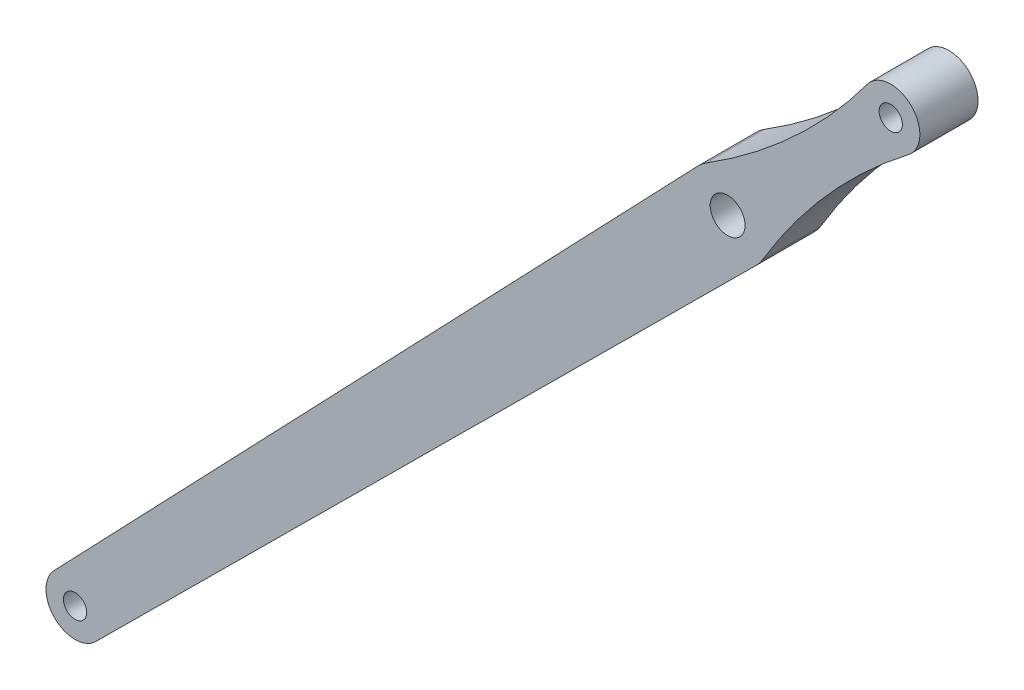
SolidWorks part; units mm, degrees
ref_plane "Front Plane" through (0, 0, 0) normal (0, 0, 1) x (1, 0, 0)
ref_plane "Top Plane" through (0, 0, 0) normal (0, 1, 0) x (1, 0, 0)
ref_plane "Right Plane" through (0, 0, 0) normal (1, 0, 0) x (0, 0, -1)
sketch "Sketch1" plane through (0, 0, 0) normal (0, 0, 1) x (1, 0, 0)
  line L0 (-124.7039, 115.7855) -> (-238.2136, 3.04) construction
  line L3 (-134.6926, 125.5935) -> (-245.3484, 10.0457) construction
  line L4 (-124.7039, 115.7855) -> (-238.2136, 3.04)
  line L5 (-134.6926, 125.5935) -> (-245.3484, 10.0457)
  arc A5 (-98.5698, 145.3249) -> (-123.6242, 117.1676) centre (-37.7285, 65.9629) ccw construction
  arc A6 (-133.3304, 126.6982) -> (-105.6348, 152.2622) centre (-186.0937, 211.6455) ccw construction
  circle A13 centre (-101.6119, 149.293) radius 5 construction
  circle A14 centre (-241.7372, 6.5874) radius 5 construction
  circle A15 centre (-129.6369, 120.7519) radius 7 construction
  circle A16 centre (-101.6119, 149.293) radius 2 construction
  circle A17 centre (-129.6369, 120.7519) radius 3 construction
  circle A18 centre (-241.7372, 6.5874) radius 2 construction
  arc A19 (-98.5698, 145.3249) -> (-123.6242, 117.1676) centre (-37.7285, 65.9629) ccw
  arc A20 (-133.3304, 126.6982) -> (-105.6348, 152.2622) centre (-186.0937, 211.6455) ccw
  circle A21 centre (-101.6119, 149.293) radius 5
  circle A22 centre (-241.7372, 6.5874) radius 5
  circle A23 centre (-129.6369, 120.7519) radius 7
  circle A24 centre (-101.6119, 149.293) radius 2
  circle A25 centre (-129.6369, 120.7519) radius 3
  circle A26 centre (-241.7372, 6.5874) radius 2
extrude "Boss-Extrude1" add sketch "Sketch1" along normal blind 5 and the other way blind 5 contours A23 L5 A22 L4 | A22 A26 | A21 A24 | A23 A19 A21 A20 | A23 A25 region at (-183.4874, 65.9098, 0) region at (-134.4026, 115.8985, 0) region at (-245.1413, 3.1207, 0) region at (-115.5195, 135.1294, 0) region at (-105.0159, 145.8263, 0)
